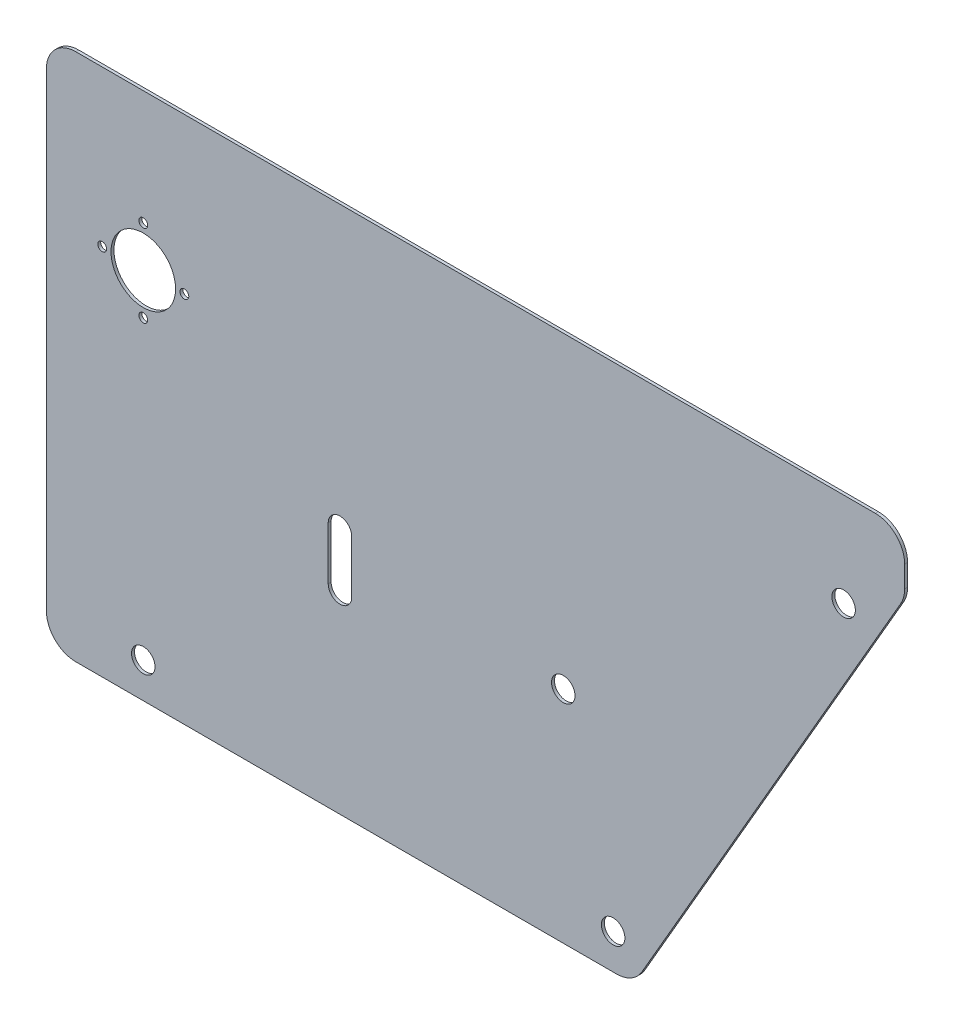
SolidWorks part; units mm, degrees
ref_plane "Front Plane" through (0, 0, 0) normal (0, 0, 1) x (1, 0, 0)
ref_plane "Top Plane" through (0, 0, 0) normal (0, 1, 0) x (1, 0, 0)
ref_plane "Right Plane" through (0, 0, 0) normal (1, 0, 0) x (0, 0, -1)
sketch "Sketch1" plane through (0, 0, 0) normal (0, 0, 1) x (1, 0, 0)
  line L0 (100, 80) -> (192.376, 80)
  line L1 (-100, -80) -> (100, -80)
  line L2 (-100, -80) -> (-100, 80)
  line L3 (-100, 80) -> (100, 80)
  line L4 (100, -80) -> (100, 80)
  line L5 (-100, -80) -> (100, 80) construction
  line L6 (-100, 80) -> (100, -80) construction
  line L7 (192.376, 80) -> (100, -80)
  line L8 (100, 80) -> (100, -80)
  line L10 (-100, 80) -> (192.376, 80)
  line L11 (-100, 80) -> (-100, 100)
  line L12 (-100, 100) -> (192.376, 100)
  line L13 (192.376, 80) -> (192.376, 100)
  point P0 (0, 0)
  dimension "D1" = 160
  dimension "D2" = 200
  dimension "D3" = 30
  dimension "D4" = 20
extrude "Boss-Extrude1" add sketch "Sketch1" along normal blind 1 contours L1 L4 L3 L2 | L7 L0 L4 | L11 L10 L13 L12 region at (0, 0, 0) region at (130.792, 26.6667, 0)
fillet "Fillet1" radius 10 5 edges at (100, -80, 0.5) (-100, -80, 0.5) (192.376, 100, 0.5) (192.376, 80, 0.5) (-100, 100, 0.5)
sketch "Sketch2" plane through (0, 0, 1) normal (0, 0, 1) x (1, 0, 0)
  line L0 (-90, -80) -> (94.2265, -80) construction
  line L1 (191.0363, 77.6795) -> (102.8868, -75) construction
  line L3 (-100, -70) -> (-100, 90) construction
  line L4 (0, -14) -> (0, 4) construction
  line L5 (-4, -14) -> (-4, 4)
  line L6 (4, -14) -> (4, 4)
  line L7 (-90, 100) -> (182.376, 100) construction
  line L8 (0, -0.55) -> (0, 0.55) construction
  circle A0 centre (93.0718, -68) radius 4
  circle A1 centre (171.5914, 68) radius 4
  circle A2 centre (-67, 47) radius 11
  circle A3 centre (-67, -68) radius 4
  circle A4 centre (-53, 47) radius 1.5
  circle A5 centre (-67, 61) radius 1.5
  circle A6 centre (-81, 47) radius 1.5
  circle A7 centre (-67, 33) radius 1.5
  arc A8 (-4, -14) -> (4, -14) centre (0, -14) ccw
  arc A9 (4, 4) -> (-4, 4) centre (0, 4) ccw
  circle A10 centre (76.0815, -5) radius 4
  point P8 (0, 0)
  point P24 (0, -5)
  dimension "D3" = 8
  dimension "D4" = 8
  dimension "D9" = 22
  dimension "D10" = 8
  dimension "D12" = 3
  dimension "D13" = 3
  dimension "D14" = 3
  dimension "D15" = 3
  dimension "D16" = 14
  dimension "D20" = 4
  dimension "D22" = 8
  dimension "D1" = 12
  dimension "D2" = 12
  dimension "D5" = 32
  dimension "D6" = 12
  dimension "D7" = 53
  dimension "D8" = 33
  dimension "D11" = 12
  dimension "D17" = 14
  dimension "D18" = 14
  dimension "D19" = 14
  dimension "D21" = 18
  dimension "D23" = 105
  dimension "D24" = 105
extrude "Cut-Extrude1" cut sketch "Sketch2" against normal blind 3
